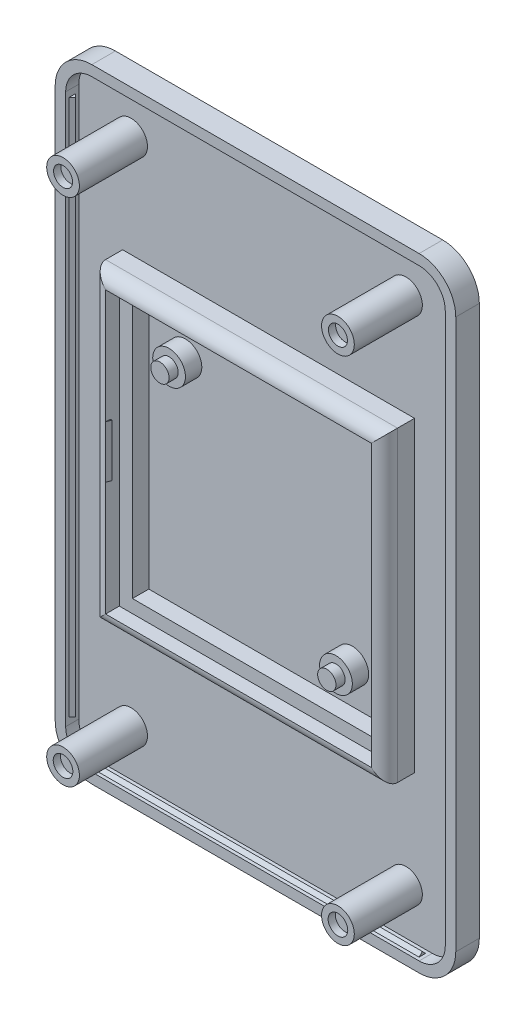
SolidWorks part; units mm, degrees
ref_plane "Front Plane" through (0, 0, 0) normal (0, 0, 1) x (1, 0, 0)
ref_plane "Top Plane" through (0, 0, 0) normal (0, 1, 0) x (1, 0, 0)
ref_plane "Right Plane" through (0, 0, 0) normal (1, 0, 0) x (0, 0, -1)
sketch "Esquisse2" plane through (0, 0, 0) normal (0, 0, 1) x (1, 0, 0)
  line L1 (-29, -46) -> (29, -46)
  line L2 (-29, -46) -> (-29, 46)
  line L3 (-29, 46) -> (29, 46)
  line L4 (29, -46) -> (29, 46)
  line L5 (-29, -46) -> (29, 46) construction
  line L6 (-29, 46) -> (29, -46) construction
  point P0 (0, 0)
  dimension "D1" = 92
  dimension "D2" = 58
extrude "Boss.-Extru.1" add sketch "Esquisse2" against normal blind 1.6
fillet "Congé1" radius 4 4 edges at (-29, 46, -0.8) (29, 46, -0.8) (29, -46, -0.8) (-29, -46, -0.8)
sketch "Esquisse3" plane through (0, 0, 0) normal (0, 0, 1) x (1, 0, 0)
  line L1 (20.3, -21.45) -> (-20.3, -21.45)
  line L2 (20.3, -21.45) -> (20.3, 21.45)
  line L3 (20.3, 21.45) -> (-20.3, 21.45)
  line L4 (-20.3, -21.45) -> (-20.3, 21.45)
  line L5 (20.3, -21.45) -> (-20.3, 21.45) construction
  line L6 (20.3, 21.45) -> (-20.3, -21.45) construction
  point P0 (0, 0)
  dimension "D1" = 42.9
  dimension "D2" = 40.6
extrude "Extru.-Mince1" add sketch "Esquisse3" along normal blind 2.5 thin contours L4 L3 L2 L1 thin type one direction reverse wall 2
sketch "Esquisse4" plane through (0, 0, 0) normal (0, 0, 1) x (1, 0, 0)
  line L0 (20.3, 21.45) -> (-20.3, 21.45) construction
  line L1 (-12.7, 13.95) -> (-20.2, 13.95)
  line L2 (-12.7, 13.95) -> (-12.7, 21.45)
  line L3 (-12.7, 21.45) -> (-20.2, 21.45)
  line L4 (-20.2, 13.95) -> (-20.2, 21.45)
  line L5 (-12.7, 13.95) -> (-20.2, 21.45) construction
  line L6 (-12.7, 21.45) -> (-20.2, 13.95) construction
  circle A0 centre (-12.7, 13.95) radius 2.5
  point P0 (-16.45, 17.7)
  dimension "D1" = 7.5
  dimension "D2" = 7.5
extrude "Boss.-Extru.2" add sketch "Esquisse4" along normal blind 2.5 contours A0
sketch "Esquisse5" plane through (0, 0, 0) normal (0, 0, 1) x (1, 0, 0)
  circle A0 centre (-12.7, 13.95) radius 1.4
extrude "Boss.-Extru.3" add sketch "Esquisse5" along normal blind 3.9
sketch "Esquisse6" plane through (0, 0, 0) normal (0, 0, 1) x (1, 0, 0)
  line L1 (20.3, -21.45) -> (12.8, -21.45) construction
  line L2 (20.3, -21.45) -> (20.3, -13.95) construction
  line L3 (20.3, -13.95) -> (12.8, -13.95) construction
  line L4 (12.8, -21.45) -> (12.8, -13.95)
  circle A0 centre (12.8, -13.95) radius 2.5
  dimension "D1" = 7.5
  dimension "D2" = 7.5
extrude "Boss.-Extru.4" add sketch "Esquisse6" along normal blind 2.5 contours A0
sketch "Esquisse7" plane through (0, 0, 0) normal (0, 0, 1) x (1, 0, 0)
  circle A0 centre (12.8, -13.95) radius 1.4
extrude "Boss.-Extru.5" add sketch "Esquisse7" along normal blind 3.9 contours A0
sketch "Esquisse8" plane through (0, 0, 0) normal (0, 0, 1) x (1, 0, 0)
  line L1 (20.3, -21.45) -> (-20.3, -21.45)
  line L2 (20.3, -21.45) -> (20.3, 21.45)
  line L3 (20.3, 21.45) -> (-20.3, 21.45)
  line L4 (-20.3, -21.45) -> (-20.3, 21.45)
extrude "Extru.-Mince2" add sketch "Esquisse8" along normal blind 4.6 thin thin type one direction wall 2
fillet "Congé2" radius 2 4 edges at (22.3, 0, 4.6) (0, 23.45, 4.6) (-22.3, 0, 4.6) (0, -23.45, 4.6)
sketch "Esquisse10" plane through (0, 0, 0) normal (0, 0, 1) x (1, 0, 0)
  line L1 (21, -39) -> (-21, -39)
  line L2 (21, -39) -> (21, 39)
  line L3 (21, 39) -> (-21, 39)
  line L4 (-21, -39) -> (-21, 39)
  line L5 (21, -39) -> (-21, 39) construction
  line L6 (21, 39) -> (-21, -39) construction
  circle A0 centre (21, -39) radius 2.5
  circle A1 centre (-21, -39) radius 2.5
  circle A2 centre (-21, 39) radius 2.5
  circle A3 centre (21, 39) radius 2.5
  point P0 (0, 0)
  dimension "D1" = 78
  dimension "D2" = 42
extrude "Boss.-Extru.6" add sketch "Esquisse10" along normal blind 10.4 contours A1 | A0 | A3 | A2
sketch "Esquisse13" plane through (0, 0, 10.4) normal (0, 0, 1) x (1, 0, 0)
  circle A0 centre (21, -39) radius 1.5
  circle A1 centre (-21, -39) radius 1.5
  circle A2 centre (-21, 39) radius 1.45
  circle A3 centre (21, 39) radius 1.45
extrude "Enlèv. mat.-Extru.1" cut sketch "Esquisse13" against normal blind 1.1
sketch "Esquisse14" plane through (0, 0, 0) normal (0, 0, 1) x (1, 0, 0)
  line L0 (25, 46) -> (-25, 46) construction
  line L1 (29, -42) -> (29, 42) construction
  line L2 (-29, 42) -> (-29, -42) construction
  line L3 (-25, -46) -> (25, -46) construction
  line L4 (25, 46) -> (-25, 46)
  line L5 (29, -42) -> (29, 42)
  line L6 (-29, 42) -> (-29, -42)
  line L7 (-25, -46) -> (25, -46)
  arc A0 (-25, 46) -> (-29, 42) centre (-25, 42) ccw construction
  arc A1 (29, 42) -> (25, 46) centre (25, 42) ccw construction
  arc A2 (25, -46) -> (29, -42) centre (25, -42) ccw construction
  arc A3 (-29, -42) -> (-25, -46) centre (-25, -42) ccw construction
  arc A4 (-25, 46) -> (-29, 42) centre (-25, 42) ccw
  arc A5 (29, 42) -> (25, 46) centre (25, 42) ccw
  arc A6 (25, -46) -> (29, -42) centre (25, -42) ccw
  arc A7 (-29, -42) -> (-25, -46) centre (-25, -42) ccw
extrude "Extru.-Mince3" add sketch "Esquisse14" along normal blind 2 and the other way blind 1.6 thin thin type one direction wall 1.6
sketch3d "Esquisse3D7"
  line L0 (20.3, -21.45, 4.6) -> (20.3, 0, 4.6) construction
  line L1 (20.3, -21.45, 4.6) -> (20.3, 21.45, 4.6) construction
  line L2 (20.3, 0, 4.6) -> (20.3, 0, 3.9)
  line L3 (20.3, 0, 4.6) -> (20.05, 0, 3.9)
  line L4 (20.05, 0, 3.9) -> (20.3, 0, 3.9)
extrude "Boss.-Extru.9" add sketch "Esquisse3D7" along direction (0, 1, 0) on the side of the normal blind 4 and the other way blind 4 contours L3 L4 L2
sketch3d "Esquisse3D8"
  line L0 (-20.3, 0, 4.6) -> (-20.0062, 0, 3.9153)
  line L1 (-20.3, 21.45, 4.6) -> (-20.3, -21.45, 4.6) construction
  line L2 (-20.0062, 0, 3.9153) -> (-20.2371, 0, 3.8947)
  line L3 (-20.2371, 0, 3.8947) -> (-20.3, 0, 4.6)
extrude "Boss.-Extru.10" add sketch "Esquisse3D8" along direction (0, -1, 0) on the side of the normal blind 4 and the other way blind 4 separate body
sketch "Esquisse16" plane through (29, 0, 0) normal (-1, 0, 0) x (0, 0, 1)
  line L0 (2, 0) -> (0, 0)
  line L1 (2, -42) -> (2, 42) construction
  line L2 (0, -42) -> (0, 42) construction
sketch3d "Esquisse3D9"
  line L2 (29, 0, 1) -> (29, 0, 1.5)
  line L3 (29, 0, 2) -> (29, 0, 0) construction
  line L4 (29, 0, 1) -> (29, 0, 0.5)
  line L6 (20.3, -21.45, 4.6) -> (20.3, -4, 4.6) construction
  line L7 (29, 0, 1.5) -> (28.5, 0, 1)
  line L8 (28.5, 0, 1) -> (29, 0, 0.5)
extrude "Boss.-Extru.11" add sketch "Esquisse3D9" along direction (0, 1, 0) on the side of the normal blind 41 and the other way blind 41
mirror "Symétrie1" about plane through (0, 0, 0) normal (1, 0, 0) of "Boss.-Extru.11"
sketch "Esquisse19" plane through (0, 46, 0) normal (0, -1, 0) x (-1, 0, 0)
  line L0 (0, -2) -> (0, 0) construction
  line L1 (-25, -2) -> (25, -2) construction
  line L2 (-25, 0) -> (25, 0) construction
  line L3 (0, -1) -> (0, -1.5)
  line L4 (0, -1) -> (0, -0.5)
sketch3d "Esquisse3D12"
  line L2 (0, 46, 1.5) -> (0, 45.5, 1)
  line L3 (0, 45.5, 1) -> (0, 46, 0.5)
  line L5 (0, 46, 1.5) -> (0, 46, 0.5)
  point P3 (0, 0, 0)
  dimension "D1" = 90
extrude "Boss.-Extru.12" add sketch "Esquisse3D12" along direction (-1, 0, 0) on the side of the normal blind 24.5 and the other way blind 24.5
mirror "Symétrie2" about plane through (0, 0, 0) normal (0, 1, 0) of "Boss.-Extru.12"
sketch "Esquisse31" plane through (0, 0, -1.6) normal (0, 0, -1) x (-1, 0, 0)
  spline S0 degree 3 poles (4.3492, -9.9887) (3.9683, -9.8345) (3.6961, -9.4898) (3.6327, -9.0816) knots 0 0 0 0 1 1 1 1
  spline S1 degree 3 poles (3.6327, -9.0816) (3.5873, -8.8458) (3.6327, -8.6825) (3.9955, -8.0295) knots 1 1 1 1 2 2 2 2
  spline S2 degree 3 poles (3.9955, -8.0295) (5.356, -5.5805) (6.0544, -2.8141) (6.0181, -0.0113) knots 2 2 2 2 3 3 3 3
  spline S3 degree 3 poles (6.0181, -0.0113) (6.0544, 2.7098) (5.3923, 5.3673) (4.0862, 7.7528) knots 3 3 3 3 4 4 4 4
  spline S4 degree 3 poles (4.0862, 7.7528) (3.8957, 8.1519) (3.7234, 8.5329) (3.5782, 8.941) knots 4 4 4 4 5 5 5 5
  spline S5 degree 3 poles (3.5782, 8.941) (3.6327, 9.2857) (3.805, 9.6032) (4.0862, 9.7937) knots 5 5 5 5 6 6 6 6
  spline S6 degree 3 poles (4.0862, 9.7937) (4.4943, 10.0113) (4.9932, 9.966) (5.3651, 9.712) knots 6 6 6 6 7 7 7 7
  spline S7 degree 3 poles (5.3651, 9.712) (5.619, 9.3855) (5.8367, 9.059) (6.0181, 8.678) knots 7 7 7 7 8 8 8 8
  spline S8 degree 3 poles (6.0181, 8.678) (6.9977, 6.7914) (7.6599, 4.7959) (7.9864, 2.7098) knots 8 8 8 8 9 9 9 9
  spline S9 degree 3 poles (7.9864, 2.7098) (8.195, 1.068) (8.2222, -0.6009) (8.068, -2.2517) knots 9 9 9 9 10 10 10 10
  spline S10 degree 3 poles (8.068, -2.2517) (7.7868, -4.3741) (7.161, -6.424) (6.1995, -8.3379) knots 10 10 10 10 11 11 11 11
  spline S11 degree 3 poles (6.1995, -8.3379) (5.619, -9.4989) (5.2925, -9.9887) (4.9478, -9.9887) knots 11 11 11 11 12 12 12 12
  spline S12 degree 3 poles (4.9478, -9.9887) (4.8753, -9.9887) (4.7937, -9.9887) (4.7211, -9.9887) knots 12 12 12 12 13 13 13 13
  spline S13 degree 3 poles (4.7211, -9.9887) (4.5941, -9.9887) (4.4762, -9.9887) (4.3492, -9.9887) knots 13 13 13 13 14 14 14 14
  spline S14 degree 3 poles (0.3946, -7.9388) (0.3946, -7.9539) (0.3946, -7.969) (0.3946, -7.9841) knots 9 9 9 9 10 10 10 10
  spline S15 degree 3 poles (2.4444, -5.907) (1.6825, -7.6213) (1.1474, -8.1746) (0.3946, -7.9388) knots 8 8 8 8 9 9 9 9
  spline S16 degree 3 poles (2.9524, 4.5782) (4.1134, 1.1406) (3.932, -2.6054) (2.4444, -5.907) knots 7 7 7 7 8 8 8 8
  spline S17 degree 3 poles (1.4014, 7.6984) (2.0544, 6.737) (2.5714, 5.6848) (2.9524, 4.5782) knots 6 6 6 6 7 7 7 7
  spline S18 degree 3 poles (-0.1497, 7.5714) (0.2494, 8.0159) (0.9116, 8.0794) (1.4014, 7.6984) knots 5 5 5 5 6 6 6 6
  spline S19 degree 3 poles (0.1224, 5.7574) (-0.449, 6.9002) (-0.4853, 7.0816) (-0.1497, 7.5714) knots 4 4 4 4 5 5 5 5
  spline S20 degree 3 poles (1.5193, 1.0227) (1.3923, 2.6825) (0.9116, 4.2971) (0.1224, 5.7574) knots 3 3 3 3 4 4 4 4
  spline S21 degree 3 poles (0.195, -5.6712) (1.2653, -3.6122) (1.7279, -1.2902) (1.5193, 1.0227) knots 2 2 2 2 3 3 3 3
  spline S22 degree 3 poles (-0.3401, -6.7868) (-0.3401, -6.678) (-0.059, -6.1791) (0.195, -5.6712) knots 1 1 1 1 2 2 2 2
  spline S23 degree 3 poles (0.3946, -7.9841) (-0.1224, -7.839) (-0.449, -7.3129) (-0.3401, -6.7868) knots 0 0 0 0 1 1 1 1
  spline S24 degree 3 poles (-3.6871, -5.907) (-3.6871, -5.9252) (-3.6871, -5.9433) (-3.6871, -5.9615) knots 10 10 10 10 11 11 11 11
  spline S25 degree 3 poles (-3.1701, -5.9887) (-3.3424, -6.0068) (-3.5238, -5.9887) (-3.6871, -5.907) knots 9 9 9 9 10 10 10 10
  spline S26 degree 3 poles (-1.9456, -4.7279) (-2.4354, -5.6803) (-2.6803, -5.907) (-3.1701, -5.9887) knots 8 8 8 8 9 9 9 9
  spline S27 degree 3 poles (-0.7937, -0.0113) (-0.7574, -1.6531) (-1.1565, -3.2857) (-1.9456, -4.7279) knots 7 7 7 7 8 8 8 8
  spline S28 degree 3 poles (-1.9546, 4.6054) (-1.1837, 3.1905) (-0.7846, 1.6032) (-0.7937, -0.0113) knots 6 6 6 6 7 7 7 7
  spline S29 degree 3 poles (-3.3515, 5.9116) (-2.771, 5.9116) (-2.4444, 5.6304) (-1.9546, 4.6054) knots 5 5 5 5 6 6 6 6
  spline S30 degree 3 poles (-4.0499, 5.6485) (-3.8776, 5.8481) (-3.6236, 5.9478) (-3.3515, 5.9116) knots 4 4 4 4 5 5 5 5
  spline S31 degree 3 poles (-3.941, 3.8345) (-4.5306, 4.9773) (-4.5306, 5.2132) (-4.0499, 5.6485) knots 3 3 3 3 4 4 4 4
  spline S32 degree 3 poles (-3.941, -4.0385) (-2.5896, -1.5896) (-2.5896, 1.3855) (-3.941, 3.8345) knots 2 2 2 2 3 3 3 3
  spline S33 degree 3 poles (-4.3492, -5.1814) (-4.3492, -5) (-4.3492, -4.7642) (-3.941, -4.0385) knots 1 1 1 1 2 2 2 2
  spline S34 degree 3 poles (-3.6871, -5.9615) (-4.0136, -5.8163) (-4.2585, -5.5261) (-4.3492, -5.1814) knots 0 0 0 0 1 1 1 1
  spline S35 degree 3 poles (-7.4966, -4.0295) (-7.4996, -4.0295) (-7.5026, -4.0295) (-7.5057, -4.0295) knots 9 9 9 9 10 10 10 10
  spline S36 degree 3 poles (-5.9637, -3.3039) (-6.4263, -4.0023) (-6.9524, -4.2109) (-7.4966, -4.0295) knots 8 8 8 8 9 9 9 9
  spline S37 degree 3 poles (-5.9637, 3.2902) (-4.6485, 1.2857) (-4.6485, -1.2993) (-5.9637, -3.3039) knots 7 7 7 7 8 8 8 8
  spline S38 degree 3 poles (-7.2517, 4.0975) (-6.7619, 4.1882) (-6.4172, 3.9796) (-5.9637, 3.2902) knots 6 6 6 6 7 7 7 7
  spline S39 degree 3 poles (-8.1587, 2.873) (-8.2585, 3.4444) (-7.8776, 3.9887) (-7.2517, 4.0975) knots 5 5 5 5 6 6 6 6
  spline S40 degree 3 poles (-7.7596, 2.1565) (-7.9138, 2.3832) (-8.0408, 2.6281) (-8.1587, 2.873) knots 4 4 4 4 5 5 5 5
  spline S41 degree 3 poles (-7.1701, -0.0113) (-7.1066, 0.7596) (-7.3152, 1.5215) (-7.7596, 2.1565) knots 3 3 3 3 4 4 4 4
  spline S42 degree 3 poles (-7.7959, -2.1519) (-7.3424, -1.5351) (-7.1247, -0.7732) (-7.1701, -0.0113) knots 2 2 2 2 3 3 3 3
  spline S43 degree 3 poles (-8.1587, -3.322) (-8.2494, -3.0045) (-8.1587, -2.7324) (-7.7959, -2.1519) knots 1 1 1 1 2 2 2 2
  spline S44 degree 3 poles (-7.5057, -4.0295) (-7.805, -3.8844) (-8.0408, -3.6395) (-8.1587, -3.322) knots 0 0 0 0 1 1 1 1
extrude "Enlèv. mat.-Extru.4" cut sketch "Esquisse31" against normal blind 0.6
